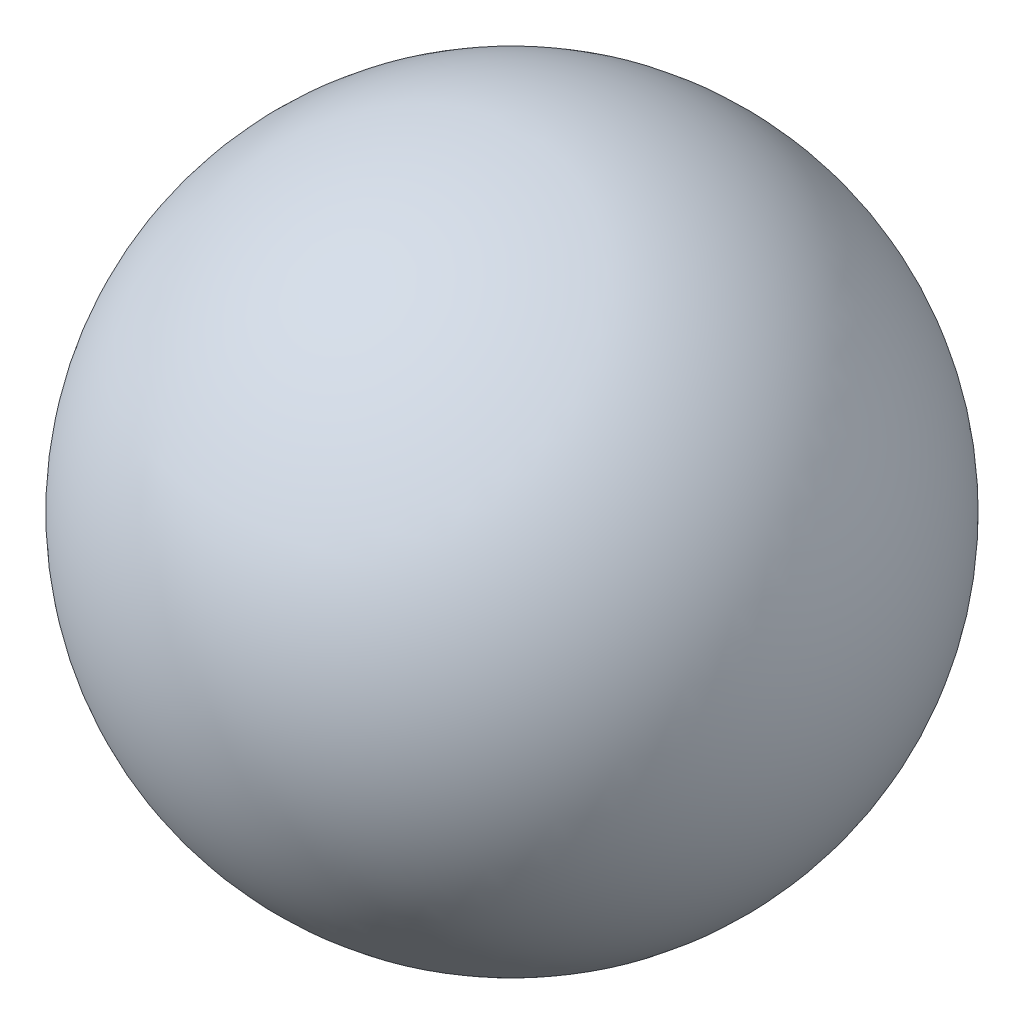
SolidWorks part; units mm, degrees
ref_plane "Front Plane" through (0, 0, 0) normal (0, 0, 1) x (1, 0, 0)
ref_plane "Top Plane" through (0, 0, 0) normal (0, 1, 0) x (1, 0, 0)
ref_plane "Right Plane" through (0, 0, 0) normal (1, 0, 0) x (0, 0, -1)
sketch "Sketch1" plane through (0, 0, 0) normal (0, 0, 1) x (1, 0, 0)
  line L0 (0, 0) -> (0, 30)
  circle A0 centre (0, 15) radius 15
  dimension "D1" = 30
revolve "Revolve3" add sketch "Sketch1" angle 360 about L0 region at (-6.3662, 15, 0)
